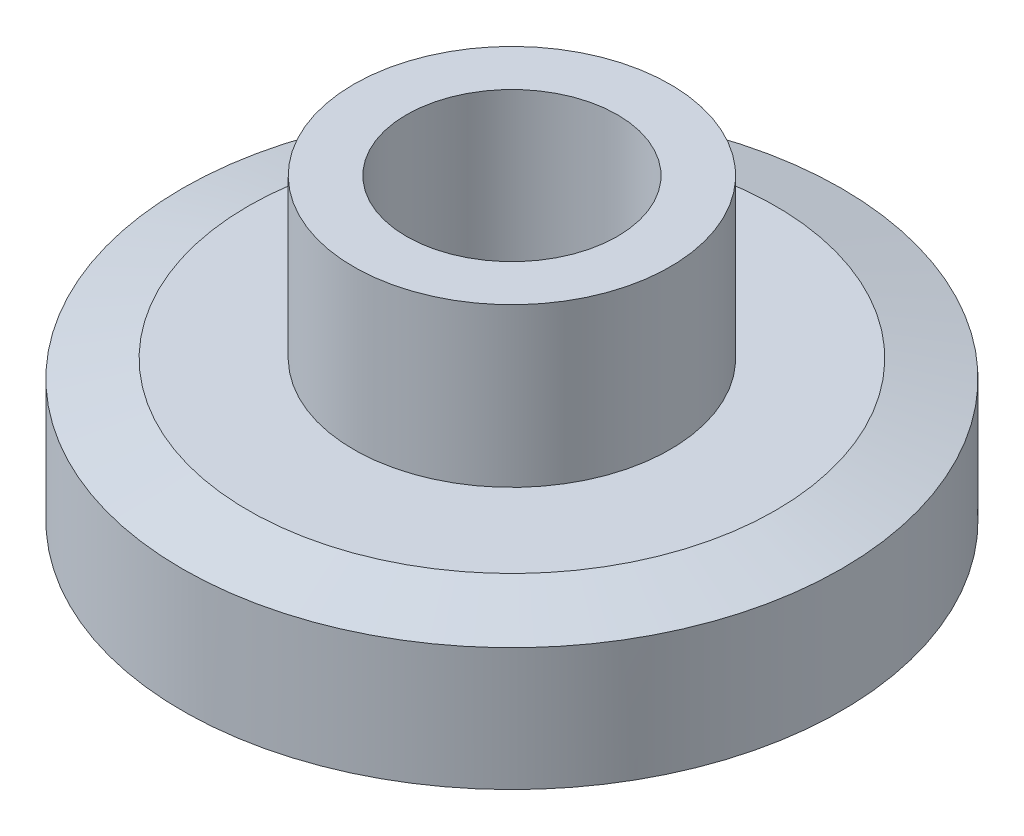
SolidWorks part; units mm, degrees
material "Сталь ШХ15 ГОСТ 801-78"
ref_plane "Plane1" through (0, 0, 0) normal (0, 0, 1) x (1, 0, 0)
ref_plane "Plane2" through (0, 0, 0) normal (0, 1, 0) x (1, 0, 0)
ref_plane "Plane3" through (0, 0, 0) normal (1, 0, 0) x (0, 0, -1)
sketch "Эскиз2" plane through (0, 0, 0) normal (0, 0, 1) x (1, 0, 0)
  line L0 (0, 0) -> (6.25, 0)
  line L1 (6.25, 0) -> (6.25, 3)
  line L2 (6.25, 3) -> (3, 3)
  line L3 (3, 3) -> (3, 6)
  line L4 (3, 6) -> (0, 6)
  line L5 (0, 6) -> (0, 0)
  dimension "D1" = 6.25
  dimension "D2" = 3
  dimension "D3" = 3
  dimension "D4" = 3
ref_axis "Ось1" through (0, 6, 0) along (0, -1, 0)
revolve "Повернуть2" add sketch "Эскиз2" angle 360 about axis through (0, 6, 0) along (0, -1, 0)
chamfer "Фаска2" distance 1.25 angle 15 1 edges at (-6.25, 3, 0) first distance on face at (-3, 3, 0)
chamfer "Фаска3" distance 1.25 angle 15 1 edges at (-6.25, 0, 0) first distance on face at (-6.25, 0, 0)
sketch "Эскиз4" plane through (0, 6, 0) normal (0, 1, 0) x (1, 0, 0)
  circle A0 centre (0, 0) radius 2
  dimension "D1" = 4
extrude "Вырез-Вытянуть2" cut sketch "Эскиз4" against normal through all both contours A0
